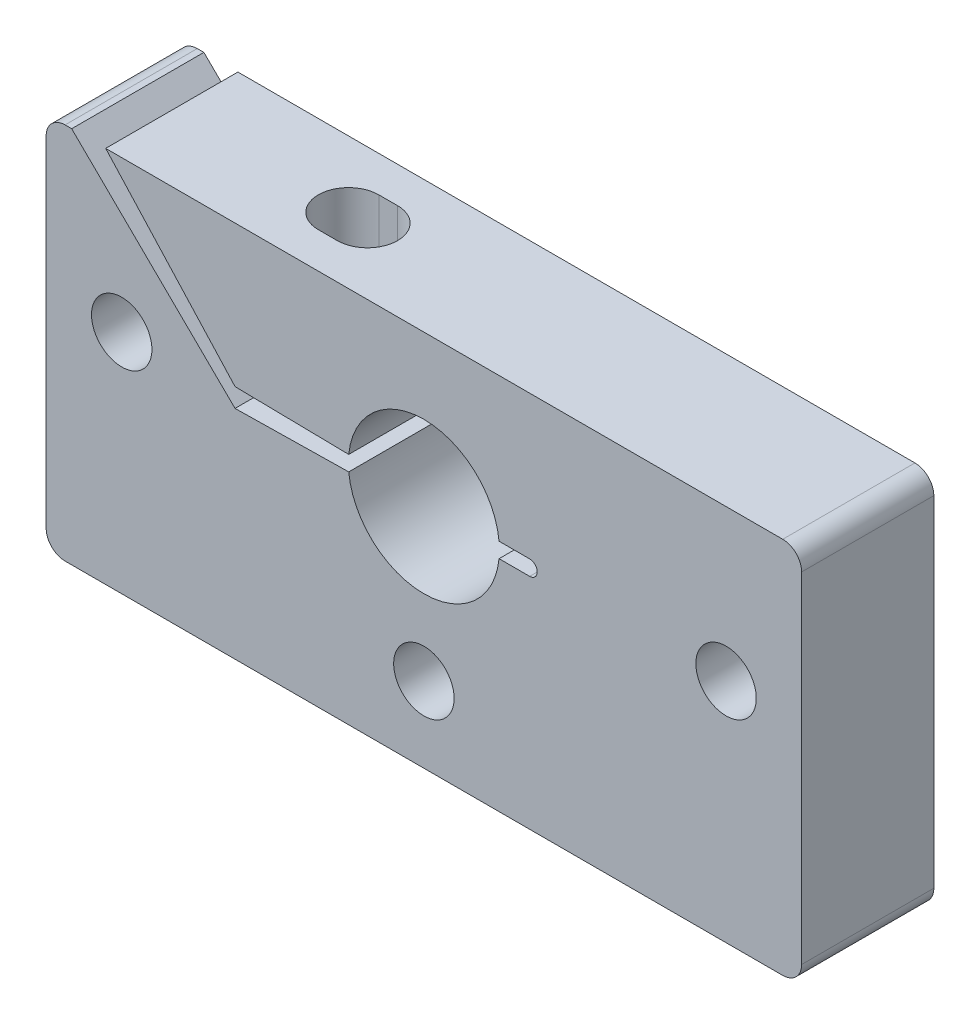
SolidWorks part; units mm, degrees
ref_plane "Front Plane" through (0, 0, 0) normal (0, 0, 1) x (1, 0, 0)
ref_plane "Top Plane" through (0, 0, 0) normal (0, 1, 0) x (1, 0, 0)
ref_plane "Right Plane" through (0, 0, 0) normal (1, 0, 0) x (0, 0, -1)
sketch "Sketch1" plane through (0, 0, 0) normal (0, 0, 1) x (1, 0, 0)
  line L0 (-43.3338, 0) -> (30.2546, 0) construction
  line L1 (-10, 0) -> (-19.1197, 9.4437) construction
  line L2 (-20, 8) -> (-18.6497, 8)
  line L3 (-20, 8) -> (-20, -12)
  line L4 (-20, -12) -> (20, -12)
  line L5 (20, 8) -> (20, -12)
  line L6 (-10, 0.5) -> (-3.9799, 0.4)
  line L7 (-10, 0.5) -> (-10, -0.5) construction
  line L8 (-10, -0.5) -> (-3.9799, -0.4)
  line L9 (6, 0.4) -> (6, -0.4)
  line L10 (-10, 0.5) -> (-16.8484, 8)
  line L11 (-10, -0.5) -> (-18.6497, 8)
  line L12 (3.9799, 0.4) -> (6, 0.4)
  line L13 (3.9799, -0.4) -> (6, -0.4)
  line L14 (-16.8484, 8) -> (20, 8)
  line L15 (0, 10.4655) -> (0, -11.9899) construction
  arc A0 (-3.9799, -0.4) -> (3.9799, -0.4) centre (0, 0) ccw
  arc A1 (3.9799, 0.4) -> (-3.9799, 0.4) centre (0, 0) ccw
  circle A2 centre (-16, 0) radius 2.2 construction
  circle A3 centre (-16, 0) radius 1.6
  circle A4 centre (16, 0) radius 1.6
  circle A5 centre (0, -8) radius 1.6
  dimension "D1" = 8
  dimension "D2" = 4.4
  dimension "D4" = 4
  dimension "D5" = 20
  dimension "D7" = 2
  dimension "D16" = 3.2
  dimension "D3" = 8
  dimension "D6" = 0.8
  dimension "D8" = 46
  dimension "D9" = 6
  dimension "D10" = 1.5
  dimension "D11" = 1.6
  dimension "D12" = 40
  dimension "D13" = 4
  dimension "D14" = 0.8
  dimension "D15" = 1
  dimension "D19" = 12
extrude "Boss-Extrude1" add sketch "Sketch1" along normal blind 3.5 and the other way blind 3.5
sketch "Sketch3" plane through (0, -12, 0) normal (0, -1, 0) x (1, 0, 0)
  line L0 (-10, 3.5) -> (-3.9799, 3.5) construction
  line L1 (-20, 3.5) -> (20, 3.5) construction
  line L7 (-6.99, 2.7251) -> (-6.99, -2.5156) construction
  line L10 (20, -3.5) -> (20, 3.5) construction
  circle A0 centre (-6.99, 0) radius 2.2
  circle A1 centre (-6.99, 0) radius 1.6
  point P6 (-6.99, 3.5)
  dimension "D1" = 4.4
  dimension "D2" = 3.2
extrude "Cut-Extrude1" cut sketch "Sketch3" against normal up to next contours A1
extrude "Cut-Extrude2" cut sketch "Sketch3<3>" against normal blind 6
sketch "Sketch3<3>" plane through (0, -12, 0) normal (0, -1, 0) x (1, 0, 0) same geometry as "Sketch3"
sketch "Sketch4" plane through (0, 8, 0) normal (0, 1, 0) x (1, 0, 0)
  line L0 (-7.49, 0) -> (-6.49, 0) construction
  line L1 (-7.49, 1.6) -> (-6.49, 1.6)
  line L2 (-7.49, -1.6) -> (-6.49, -1.6)
  arc A0 (-7.49, 1.6) -> (-7.49, -1.6) centre (-7.49, 0) ccw
  arc A1 (-6.49, -1.6) -> (-6.49, 1.6) centre (-6.49, 0) ccw
  point P2 (-6.99, 0)
  dimension "D1" = 3.2
  dimension "D2" = 1
extrude "Cut-Extrude3" cut sketch "Sketch4" against normal up to next
fillet "Fillet1" radius 1 4 edges at (-20, -12, 0) (20, -12, 0) (20, 8, 0) (-20, 8, 0)
fillet "Fillet2" 2 edges at (6, 0.4, 0) (6, -0.4, 0) type full round first side face at (4.99, 0.4, 0) second side face at (4.99, -0.4, 0) middle face at (6, 0, 0)
